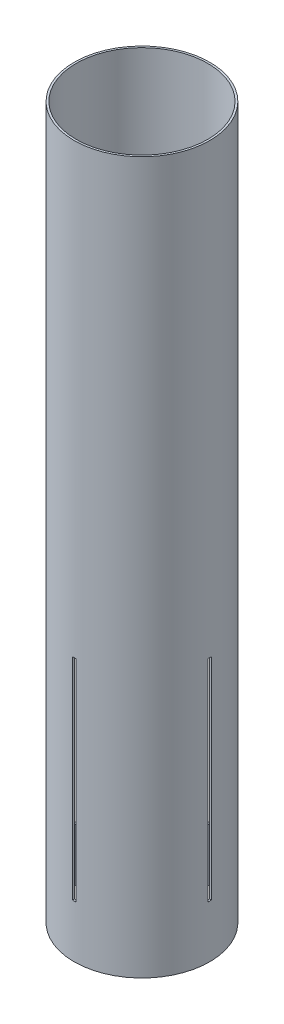
SolidWorks part; units mm, degrees
ref_plane "Front Plane" through (0, 0, 0) normal (0, 0, 1) x (1, 0, 0)
ref_plane "Top Plane" through (0, 0, 0) normal (0, 1, 0) x (1, 0, 0)
ref_plane "Right Plane" through (0, 0, 0) normal (1, 0, 0) x (0, 0, -1)
sketch "Sketch1" plane through (0, 0, 0) normal (0, 1, 0) x (1, 0, 0)
  circle A0 centre (0, 0) radius 65.405
  circle A1 centre (0, 0) radius 63.5
  dimension "D1" = 130.81
  dimension "D2" = 127
extrude "Boss-Extrude1" add sketch "Sketch1" along normal mid plane 685.8
sketch "Sketch4" plane through (0, 0, 0) normal (1, 0, 0) x (0, 0, -1)
  line L0 (0, -342.9) -> (0, 342.9)
  line L1 (-1.5875, -88.9) -> (1.5875, -88.9)
  line L2 (-1.5875, -88.9) -> (-1.5875, -292.1)
  line L3 (-1.5875, -292.1) -> (1.5875, -292.1)
  line L4 (1.5875, -88.9) -> (1.5875, -292.1)
  line L5 (-65.405, -342.9) -> (65.405, -342.9) construction
  line L6 (65.405, 342.9) -> (-65.405, 342.9) construction
  line L7 (-63.5, -342.9) -> (63.5, -342.9) construction
  line L8 (65.405, -342.9) -> (65.405, 342.9) construction
  dimension "D1" = 3.175
  dimension "D2" = 203.2
  dimension "D3" = 50.8
  dimension "D4" = 63.8175
extrude "Cut-Extrude2" cut sketch "Sketch4" along direction (1, 0, 0) on the side against the normal through all both and the other way through all contours L2 L3 L4 L1
pattern_circular "CirPattern4" count 2 every 90 about axis through (0, 342.9, 0) along (0, -1, 0) of "Cut-Extrude2" reverse direction yes
equation "\"iDiameter\"= 5in"
equation "\"oDiameter\"= 5.15in"
equation "\"length\"= 26in"
